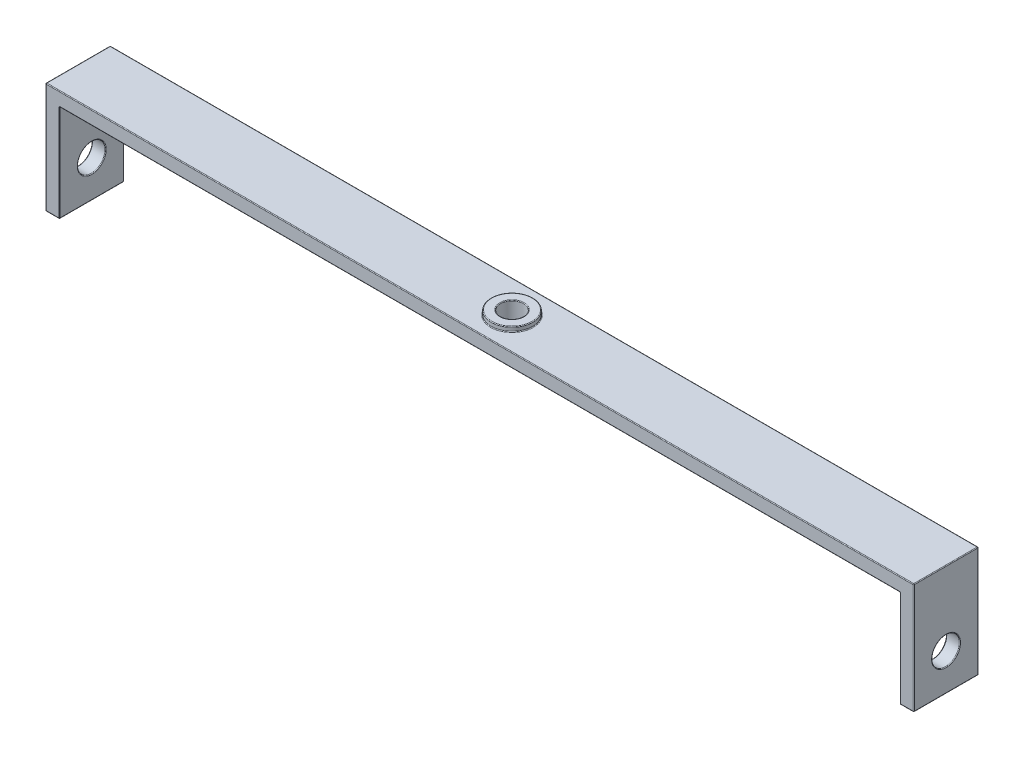
SolidWorks part; units mm, degrees
ref_plane "Front Plane" through (0, 0, 0) normal (0, 0, 1) x (1, 0, 0)
ref_plane "Top Plane" through (0, 0, 0) normal (0, 1, 0) x (1, 0, 0)
ref_plane "Right Plane" through (0, 0, 0) normal (1, 0, 0) x (0, 0, -1)
sketch "Sketch1" plane through (0, 0, 0) normal (0, 0, 1) x (1, 0, 0)
  line L0 (-47, 0) -> (47, 0)
  line L1 (47, 0) -> (47, -12)
  line L2 (-47, 0) -> (-47, -12)
  line L3 (-45.5, -1.5) -> (-45.5, -12)
  line L4 (-45.5, -1.5) -> (45.5, -1.5)
  line L5 (45.5, -1.5) -> (45.5, -12)
  line L6 (-47, -12) -> (-45.5, -12)
  line L7 (45.5, -12) -> (47, -12)
  point P2 (0, 0)
  dimension "D1" = 94
  dimension "D2" = 12
  dimension "D3" = 1.5
extrude "Boss-Extrude1" add sketch "Sketch1" along normal blind 3.5 and the other way blind 3.5
sketch "Sketch2" plane through (0, 0, 0) normal (0, 1, 0) x (1, 0, 0)
  circle A0 centre (0, 0) radius 1.25
  dimension "D1" = 2.5
extrude "Cut-Extrude1" cut sketch "Sketch2" against normal up to surface (1.5 mm away) up to face at (0, -1.5, 0)
sketch "Sketch3" plane through (0, 0, 0) normal (0, 1, 0) x (1, 0, 0)
  circle A0 centre (0, 0) radius 1.25 construction
  circle A1 centre (0, 0) radius 1.25
  circle A2 centre (0, 0) radius 2.25
  dimension "D1" = 1
extrude "Boss-Extrude2" add sketch "Sketch3" along normal blind 0.5
sketch "Sketch4" plane through (0, 0, 0) normal (1, 0, 0) x (0, 0, -1)
  line L0 (0, 0.5) -> (0, -8) construction
  line L1 (1.25, 0.5) -> (-1.25, 0.5) construction
  circle A0 centre (0, -8) radius 1.5
  dimension "D2" = 3
  dimension "D1" = 8.5
extrude "Cut-Extrude2" cut sketch "Sketch4" against normal up to surface and the other way up to surface up to face at (-47, -6, 0) other way up to face at (47, -6, 0)
fillet "Fillet1" radius 0.075 32 edges at (47, -8, -1.5) (-47, -8, 1.5) (-45.5, -8, -1.5) (45.5, -9.5, 0) (-1.25, 0.5, 0) (-2.25, 0, 0) (-2.25, 0.5, 0) (0, -1.5, -1.25) (-47, -6, 3.5) (-46.25, -12, 3.5) (-45.5, -6.75, 3.5) (0, -1.5, 3.5) (45.5, -6.75, 3.5) (46.25, -12, 3.5) (47, -6, 3.5) (-47, -6, -3.5) (-46.25, -12, -3.5) (-45.5, -6.75, -3.5) (0, -1.5, -3.5) (45.5, -6.75, -3.5) (46.25, -12, -3.5) (47, -6, -3.5) (0, 0, -3.5) (-47, -12, 0) (-45.5, -12, 0) (-45.5, -1.5, 0) (45.5, -1.5, 0) (45.5, -12, 0) (47, -12, 0) (47, 0, 0) (-47, 0, 0) (0, 0, 3.5)
